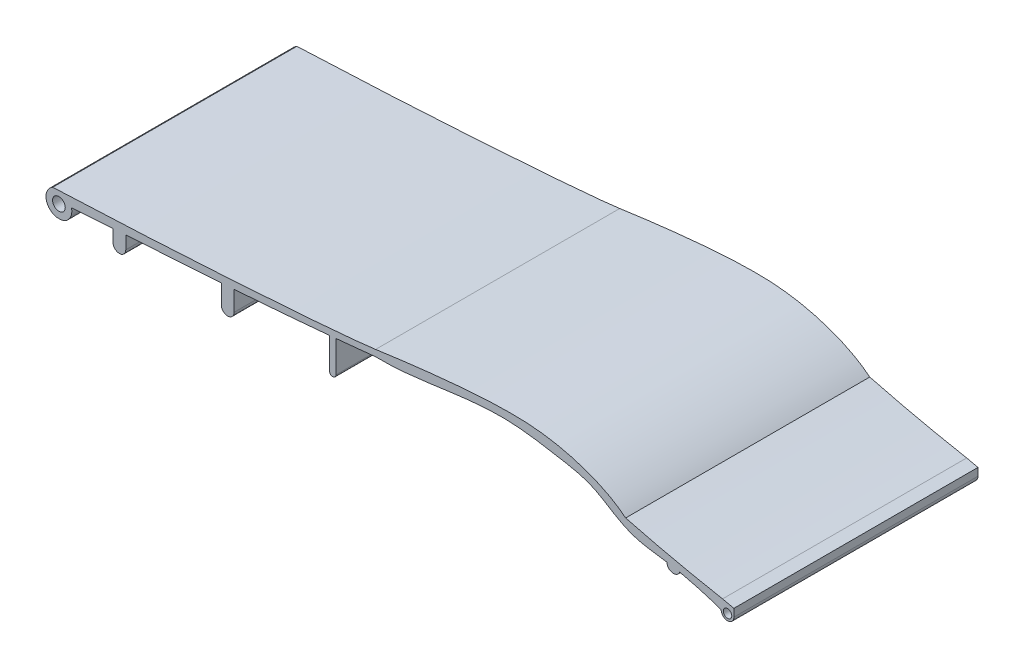
SolidWorks part; units mm, degrees
material "Balsa"
ref_plane "Front Plane" through (0, 0, 0) normal (0, 0, 1) x (1, 0, 0)
ref_plane "Top Plane" through (0, 0, 0) normal (0, 1, 0) x (1, 0, 0)
ref_plane "Right Plane" through (0, 0, 0) normal (1, 0, 0) x (0, 0, -1)
sketch "Sketch1" plane through (0, 0, 0) normal (0, 0, 1) x (1, 0, 0)
  line L0 (-268, 0) -> (-274, 0)
  line L1 (-274, 0) -> (-280, 0)
  line L2 (-280, 0) -> (-280, 11.2166)
  line L3 (-274, 5.4595) -> (-274, 6)
  line L5 (-274, 6) -> (-274, 5.4595)
  line L6 (-274, 6) -> (-274, 5.4595)
  line L8 (-70, 16) -> (-70, -46.5)
  line L9 (-70, -46.5) -> (-58, -46.5)
  line L10 (-58, -46.5) -> (-58, 16)
  line L11 (-58, 16) -> (-70, 16)
  line L70 (150, -10) -> (150, -20)
  line L71 (150, 0) -> (150, -10)
  line L72 (-7, 3.5) -> (-7, -46.5)
  line L73 (-7, 11.3618) -> (-7, 3.5)
  line L74 (0, 0) -> (-200, 0)
  line L75 (0, 0) -> (-200, 0)
  line L76 (0, 0) -> (150, 0)
  line L77 (0, 0) -> (-570, 0)
  line L78 (-7, -46.5) -> (38, -46.5)
  line L79 (38, -46.5) -> (38, 0)
  line L80 (38, 0) -> (44, 0)
  line L81 (44, 0) -> (44, -46.5)
  line L82 (44, -46.5) -> (38, -46.5)
  line L83 (-7, -46.5) -> (-13, -46.5)
  line L84 (-13, -46.5) -> (-13, 3.5)
  line L85 (-121, -46.5) -> (-166, -46.5)
  line L86 (-121, -46.5) -> (-121, 17)
  line L87 (-121, 17) -> (-115, 17)
  line L88 (-115, 17) -> (-115, -46.5)
  line L89 (-115, -46.5) -> (-121, -46.5)
  line L90 (-172, -46.5) -> (-166, -46.5)
  line L91 (-166, -46.5) -> (-166, 0)
  line L92 (-166, 0) -> (-172, 0)
  line L93 (-223, -46.5) -> (-217, -46.5)
  line L94 (-223, -46.5) -> (-268, -46.5)
  line L95 (-223, 0) -> (-223, -46.5)
  line L96 (-172, -46.5) -> (-217, -46.5)
  line L97 (-172, 0) -> (-172, -46.5)
  line L98 (-217, 0) -> (-223, 0)
  line L99 (-268, 0) -> (-223, 0)
  line L100 (-217, 0) -> (-172, 0)
  line L101 (-217, -46.5) -> (-217, 0)
  line L102 (150, 0) -> (-570, 0)
  line L103 (-274, 5.4595) -> (-274, 6)
  line L105 (-570.0024, 16.2157) -> (-570.0015, 10.2157)
  line L106 (-570.0024, 16.2157) -> (-570, 0)
  line L107 (150, -20) -> (150, -55)
  line L108 (150, -55) -> (150, -65)
  line L109 (150, -20) -> (150, 0)
  line L110 (-200, 0) -> (-200, -87.1417)
  line L111 (-200, -87.1417) -> (-200, 15.2435)
  line L112 (-124.7856, 21.2375) -> (-121, 17)
  line L113 (44, -89.7516) -> (44, -99.7516)
  line L114 (44, -99.7516) -> (-91, -99.7516)
  line L115 (-91, -99.7516) -> (-91, -89.7516)
  line L116 (-91, -89.7516) -> (44, -89.7516)
  line L117 (44, -59.7516) -> (-91, -59.7516)
  line L118 (-91, -59.7516) -> (-91, -89.7516)
  line L119 (44, -59.7516) -> (44, -89.7516)
  line L120 (44, -89.7516) -> (44, -59.7516)
  line L121 (44, -10.7516) -> (44, -59.7516)
  line L122 (44, -10.7516) -> (44, -59.7516)
  line L123 (44, -10.7516) -> (44, -59.7516)
  line L124 (44, -46.5) -> (-274, -46.5)
  line L125 (-274, 0) -> (-274, -46.5)
  line L126 (-274, -46.5) -> (-268, -46.5)
  line L127 (-286.4605, 10.9659) -> (-286.4605, 4.5334)
  line L128 (-268, 0) -> (-268, 8.629)
  line L129 (-268, -46.5) -> (-268, 0)
  line L130 (-268, 0) -> (-274, 0)
  line L131 (-426, -11.2496) -> (-426, -41.2496)
  line L132 (44, -10.7516) -> (38, -10.7516)
  line L135 (-7, 11.3618) -> (44, 0)
  line L136 (44, 0) -> (44, -10.7516)
  line L137 (38, -10.7516) -> (38, -3.6013)
  circle A0 centre (-274, 6) radius 3
  circle A2 centre (-10, 3.5) radius 3
  arc A4 (-7, 11.3618) -> (150, -10) centre (160.7975, 656.9795) ccw
  arc A5 (-570.0015, 10.2157) -> (-280, 5.0011) centre (-396.8357, 1573.962) ccw
  arc A6 (-268, 8.629) -> (-124.7856, 18.2375) centre (-325.5367, 1938.3319) ccw
  circle A7 centre (41, -3.6013) radius 3
  spline S2 degree 3 poles (150, -65) (75.3181, -107.9793) (-174.9356, -104.3379) (-414.0206, -49.0474) (-570, 0) knots 0 0 0 0 0.3348 1 1 1 1
  spline S3 degree 3 poles (-124.7856, 21.2375) (-153.5511, 17.0681) (-428.6382, -2.4062) (-576.2077, 17) knots 0 0 0 0 1 1 1 1
  spline S5 degree 3 poles (-199.3437, 0.495) (-200.1813, -0.1291) (-199.226, 0.5194) (-198.369, 1.0376) (-196.1381, 2.3769) (-193.1122, 3.8252) (-188.8712, 5.408) (-183.689, 6.8909) (-177.6267, 8.2768) (-170.7959, 9.4967) (-163.2767, 10.5098) (-155.1671, 11.2868) (-146.5636, 11.7978) (-137.5696, 12.0361) (-128.2881, 11.9963) (-118.8227, 11.681) (-109.2761, 11.1075) (-99.7479, 10.2984) (-90.3339, 9.2749) (-81.1229, 8.0828) (-72.1978, 6.7569) (-63.6354, 5.3459) (-55.5023, 3.8968) (-47.8581, 2.464) (-40.7509, 1.107) (-34.2154, -0.1398) (-28.2189, -1.1341) (-22.7323, -1.8456) (-17.7581, -2.4003) (-13.3207, -2.8103) (-9.4655, -3.0663) (-6.2354, -3.2056) (-3.6668, -3.1153) (-1.7892, -3.0221) (-0.3927, -2.3577) (-0.017, -1.0193) (0.0467, 0.4399) (-0.2836, 2.1653) (-0.9767, 4.0346) (-2.0583, 6.0034) (-3.5225, 8.0271) (-5.4287, 10.0433) (-7.7678, 12.0345) (-10.506, 14.0225) (-13.642, 15.9651) (-17.1562, 17.836) (-21.0295, 19.6139) (-25.2494, 21.2627) (-29.7898, 22.7737) (-34.6314, 24.1113) (-39.7536, 25.2521) (-45.1512, 26.1326) (-50.8254, 26.7554) (-56.7995, 27.0627) (-63.0757, 27.0793) (-69.6422, 26.9233) (-76.4655, 26.562) (-83.5076, 26.0368) (-90.7283, 25.3757) (-98.0768, 24.616) (-105.4932, 23.7718) (-112.9161, 22.8645) (-120.2861, 21.8877) (-127.55, 20.8444) (-134.6611, 19.7429) (-141.5735, 18.5812) (-148.2473, 17.3741) (-154.6405, 16.1233) (-160.7158, 14.8443) (-166.4359, 13.5437) (-171.7669, 12.2295) (-176.6782, 10.9112) (-181.1426, 9.6011) (-185.1352, 8.3052) (-188.6352, 7.0347) (-191.6263, 5.7987) (-194.104, 4.6144) (-196.0965, 3.3923) (-197.5531, 2.1801) (-198.7877, 1.0405) (-199.3437, 0.495) (-200.1813, -0.1291) (-199.226, 0.5194) knots -0.007483 -0.003649 -0.00098 0 0.001 0.004147 0.009748 0.018044 0.028864 0.041831 0.056714 0.073341 0.091508 0.111022 0.131662 0.153208 0.175433 0.19811 0.221011 0.243906 0.266573 0.28881 0.310405 0.331178 0.350944 0.369556 0.386865 0.402753 0.417196 0.43038 0.442363 0.453032 0.462284 0.470026 0.476177 0.48065 0.483553 0.486421 0.489953 0.494097 0.498851 0.504197 0.510125 0.516691 0.524012 0.532092 0.540898 0.550403 0.560581 0.571396 0.582828 0.59483 0.607347 0.620384 0.633969 0.6482 0.663194 0.678899 0.695227 0.712113 0.729459 0.747143 0.76501 0.782905 0.800688 0.818242 0.835449 0.852212 0.86843 0.884009 0.898855 0.912882 0.926011 0.938167 0.94929 0.959322 0.968217 0.975948 0.982474 0.987905 0.992517 0.996351 0.99902 1 1.001 1.004147 1.009748 only from (-200, 0) to (-200, 0)
  spline S6 degree 3 poles (-124.7856, 18.2375) (-104.0824, 17.7332) (-77.2395, 25.8381) (-49.0695, 22.1621) (-28.3585, 18.6444) (-22.2812, 16.9142) (-2.3267, 3.4627) (13.669, 4.5429) (37.1337, -3.1314) (38, -3.6013) knots 0 0 0 0 0.28574 0.361508 0.389511 0.565774 0.659519 0.859319 1 1 1 1
  dimension "D3" = 3
extrude "Boss-Extrude1" add sketch "Sketch1" along normal mid plane 115
sketch "Sketch2" plane through (0, 0, 57.5) normal (0, 0, 1) x (1, 0, 0)
  circle A0 centre (41, -3.6013) radius 2
extrude "Cut-Extrude1" cut sketch "Sketch2" against normal blind 115
sketch "Sketch3" plane through (0, 0, 57.5) normal (0, 0, 1) x (1, 0, 0)
  line L0 (-274, 12.0826) -> (-297.0333, 12.0826)
  line L1 (-297.0333, 12.0826) -> (-297.0333, -10.4449)
  line L2 (-297.0333, -10.4449) -> (-274, -10.4449)
  line L3 (-274, -10.4449) -> (-274, -0.0826)
  line L4 (-200, 11.8574) -> (-268.0857, 7.4206)
  line L5 (-274, -10.4449) -> (-200, -10.4449)
  line L6 (-200, -10.4449) -> (-200, 11.8574)
  circle A0 centre (-274, 6) radius 6.0826
  spline M7 degree 3 poles (-124.7856, 21.2375) (-153.5511, 17.0681) (-428.6382, -2.4062) (-576.2077, 17) knots 0 0 0 0 1 1 1 1 only from (-124.7856, 21.2375) to (-286.4605, 10.9659)
  line M8 (-286.4605, 10.9659) -> (-286.4605, 4.5334)
  arc M9 (-286.4605, 4.5334) -> (-280, 5.0011) centre (-396.8357, 1573.962) ccw
  line M10 (-280, 5.0011) -> (-280, 0)
  line M11 (-280, 0) -> (-200, 0)
  line M12 (-200, 0) -> (-200, 11.8574)
extrude "Cut-Extrude2" cut sketch "Sketch3" against normal up to surface (115 mm away) contours A0 M7 M8 M9 | A0 M10 M11 | A0 L4 M11 M12
sketch "Sketch4" plane through (0, 0, 0) normal (0, 0, 1) x (1, 0, 0)
  line L0 (0, 0) -> (-200, 0) construction
  line L1 (0, 0) -> (-200, 0) construction
  line L2 (-200, 0) -> (-200, -87.1417) construction
  line L3 (-200, -87.1417) -> (-200, 15.2435) construction
  line L4 (-70, 16) -> (-70, -46.5)
  line L5 (-70, -46.5) -> (-58, -46.5)
  line L6 (-58, -46.5) -> (-58, 16)
  line L7 (-58, 16) -> (-70, 16)
  line L8 (-70, 16) -> (-70, -46.5)
  line L9 (-70, -46.5) -> (-58, -46.5)
  line L10 (-58, -46.5) -> (-58, 16)
  line L11 (-58, 16) -> (-70, 16)
  line L12 (0, 0) -> (150, 0) construction
  line L13 (0, 0) -> (-570, 0) construction
  line L14 (-7, 3.5) -> (-7, -46.5) construction
  line L15 (-7, 11.3618) -> (-7, 3.5) construction
  line L16 (-7, 11.3618) -> (44, 0) construction
  line L17 (-7, -46.5) -> (38, -46.5) construction
  line L18 (-7, -46.5) -> (-13, -46.5) construction
  line L19 (-13, -46.5) -> (-13, 3.5) construction
  line L20 (150, 0) -> (150, -10) construction
  line L21 (150, 0) -> (-570, 0) construction
  line L22 (150, -20) -> (150, 0) construction
  line L23 (150, -10) -> (150, -20) construction
  line L24 (150, -20) -> (150, -55) construction
  line L25 (150, -55) -> (150, -65) construction
  line L26 (-223, -46.5) -> (-217, -46.5) construction
  line L27 (-223, -46.5) -> (-268, -46.5) construction
  line L28 (-223, 0) -> (-223, -46.5) construction
  line L29 (-166, -46.5) -> (-166, 0) construction
  line L30 (-166, 0) -> (-172, 0) construction
  line L31 (-172, 0) -> (-172, -46.5) construction
  line L32 (-217, 0) -> (-172, 0) construction
  line L33 (-172, -46.5) -> (-166, -46.5) construction
  line L34 (-172, -46.5) -> (-217, -46.5) construction
  line L35 (-121, -46.5) -> (-121, 17) construction
  line L36 (-121, 17) -> (-115, 17) construction
  line L37 (-115, 17) -> (-115, -46.5) construction
  line L38 (-115, -46.5) -> (-121, -46.5) construction
  line L39 (-124.7856, 21.2375) -> (-121, 17) construction
  line L40 (-121, -46.5) -> (-166, -46.5) construction
  line L41 (44, 0) -> (44, -46.5) construction
  line L42 (44, -46.5) -> (38, -46.5) construction
  line L43 (44, -46.5) -> (-274, -46.5) construction
  line L44 (38, -46.5) -> (38, 0) construction
  line L45 (38, 0) -> (44, 0) construction
  line L46 (44, 0) -> (44, -10.7516) construction
  line L47 (-570.0024, 16.2157) -> (-570.0015, 10.2157) construction
  line L48 (-570.0024, 16.2157) -> (-570, 0) construction
  line L49 (-217, 0) -> (-223, 0) construction
  line L50 (-217, -46.5) -> (-217, 0) construction
  line L51 (-268, 0) -> (-223, 0) construction
  line L52 (-274, -46.5) -> (-268, -46.5) construction
  line L53 (-268, -46.5) -> (-268, 0) construction
  line L54 (-274, 5.4595) -> (-274, 6) construction
  line L55 (-274, 6) -> (-274, 5.4595) construction
  line L56 (-274, 6) -> (-274, 5.4595) construction
  line L57 (-274, 5.4595) -> (-274, 6) construction
  line L58 (-268, 0) -> (-274, 0) construction
  line L59 (-274, 0) -> (-280, 0) construction
  line L60 (-280, 0) -> (-280, 11.2166) construction
  line L61 (-274, 0) -> (-274, -46.5) construction
  line L62 (-268, 0) -> (-274, 0) construction
  line L63 (44, -10.7516) -> (38, -10.7516) construction
  line L64 (38, -10.7516) -> (38, -3.6013) construction
  line L65 (-268, 0) -> (-268, 8.629) construction
  line L66 (-426, -11.2496) -> (-426, -41.2496) construction
  line L67 (-286.4605, 10.9659) -> (-286.4605, 4.5334) construction
  line L68 (44, -10.7516) -> (44, -59.7516) construction
  line L69 (44, -10.7516) -> (44, -59.7516) construction
  line L70 (44, -10.7516) -> (44, -59.7516) construction
  line L71 (44, -59.7516) -> (-91, -59.7516) construction
  line L72 (-91, -59.7516) -> (-91, -89.7516) construction
  line L73 (44, -59.7516) -> (44, -89.7516) construction
  line L74 (44, -89.7516) -> (44, -59.7516) construction
  line L75 (44, -89.7516) -> (44, -99.7516) construction
  line L76 (44, -99.7516) -> (-91, -99.7516) construction
  line L77 (-91, -99.7516) -> (-91, -89.7516) construction
  line L78 (-91, -89.7516) -> (44, -89.7516) construction
  line L79 (0, 0) -> (-200, 0)
  line L80 (0, 0) -> (-200, 0)
  line L81 (-200, 0) -> (-200, -87.1417)
  line L82 (-200, -87.1417) -> (-200, 15.2435)
  line L83 (0, 0) -> (150, 0)
  line L84 (0, 0) -> (-570, 0)
  line L85 (-7, 3.5) -> (-7, -46.5)
  line L86 (-7, 11.3618) -> (-7, 3.5)
  line L87 (-7, 11.3618) -> (44, 0)
  line L88 (-7, -46.5) -> (38, -46.5)
  line L89 (-7, -46.5) -> (-13, -46.5)
  line L90 (-13, -46.5) -> (-13, 3.5)
  line L91 (150, 0) -> (150, -10)
  line L92 (150, 0) -> (-570, 0)
  line L93 (150, -20) -> (150, 0)
  line L94 (150, -10) -> (150, -20)
  line L95 (150, -20) -> (150, -55)
  line L96 (150, -55) -> (150, -65)
  line L97 (-223, -46.5) -> (-217, -46.5)
  line L98 (-223, -46.5) -> (-268, -46.5)
  line L99 (-223, 0) -> (-223, -46.5)
  line L100 (-166, -46.5) -> (-166, 0)
  line L101 (-166, 0) -> (-172, 0)
  line L102 (-172, 0) -> (-172, -46.5)
  line L103 (-217, 0) -> (-172, 0)
  line L104 (-172, -46.5) -> (-166, -46.5)
  line L105 (-172, -46.5) -> (-217, -46.5)
  line L106 (-121, -46.5) -> (-121, 17)
  line L107 (-121, 17) -> (-115, 17)
  line L108 (-115, 17) -> (-115, -46.5)
  line L109 (-115, -46.5) -> (-121, -46.5)
  line L110 (-124.7856, 21.2375) -> (-121, 17)
  line L111 (-121, -46.5) -> (-166, -46.5)
  line L112 (44, 0) -> (44, -46.5)
  line L113 (44, -46.5) -> (38, -46.5)
  line L114 (44, -46.5) -> (-274, -46.5)
  line L115 (38, -46.5) -> (38, 0)
  line L116 (38, 0) -> (44, 0)
  line L117 (44, 0) -> (44, -10.7516)
  line L118 (-570.0024, 16.2157) -> (-570.0015, 10.2157)
  line L119 (-570.0024, 16.2157) -> (-570, 0)
  line L120 (-217, 0) -> (-223, 0)
  line L121 (-217, -46.5) -> (-217, 0)
  line L122 (-268, 0) -> (-223, 0)
  line L123 (-274, -46.5) -> (-268, -46.5)
  line L124 (-268, -46.5) -> (-268, 0)
  line L125 (-274, 5.4595) -> (-274, 6)
  line L126 (-274, 6) -> (-274, 5.4595)
  line L127 (-274, 6) -> (-274, 5.4595)
  line L128 (-274, 5.4595) -> (-274, 6)
  line L129 (-268, 0) -> (-274, 0)
  line L130 (-274, 0) -> (-280, 0)
  line L131 (-280, 0) -> (-280, 11.2166)
  line L132 (-274, 0) -> (-274, -46.5)
  line L133 (-268, 0) -> (-274, 0)
  line L134 (44, -10.7516) -> (38, -10.7516)
  line L135 (38, -10.7516) -> (38, -3.6013)
  line L136 (-268, 0) -> (-268, 8.629)
  line L137 (-426, -11.2496) -> (-426, -41.2496)
  line L138 (-286.4605, 10.9659) -> (-286.4605, 4.5334)
  line L139 (44, -10.7516) -> (44, -59.7516)
  line L140 (44, -10.7516) -> (44, -59.7516)
  line L141 (44, -10.7516) -> (44, -59.7516)
  line L142 (44, -59.7516) -> (-91, -59.7516)
  line L143 (-91, -59.7516) -> (-91, -89.7516)
  line L144 (44, -59.7516) -> (44, -89.7516)
  line L145 (44, -89.7516) -> (44, -59.7516)
  line L146 (44, -89.7516) -> (44, -99.7516)
  line L147 (44, -99.7516) -> (-91, -99.7516)
  line L148 (-91, -99.7516) -> (-91, -89.7516)
  line L149 (-91, -89.7516) -> (44, -89.7516)
  line L150 (-268, 0) -> (-223, 0)
  line L151 (-245.5, 0) -> (-242.5, 0)
  line L152 (-242.5, 0) -> (-242.5, 9.5581)
  line L153 (-242.5, 9.5581) -> (-242.5, 0)
  line L154 (-245.5, 0) -> (-248.5, 0)
  line L155 (-248.5, 0) -> (-248.5, 9.3091)
  line L156 (-217, 0) -> (-172, 0)
  line L157 (-194.5, 0) -> (-197.5, 0)
  line L158 (-197.5, 0) -> (-197.5, 12.0219)
  line L159 (-197.5, 12.0219) -> (-197.5, 0)
  line L160 (-194.5, 0) -> (-191.5, 0)
  line L161 (-191.5, 0) -> (-191.5, 12.4301)
  line L162 (-191.5, 12.4301) -> (-191.5, 0)
  line L163 (-166, 0) -> (-121, 0)
  line L164 (-121, 0) -> (-143.5, 0)
  line L165 (-143.5, 0) -> (-146.5, 0)
  line L166 (-146.5, 0) -> (-146.5, 16.0912)
  line L167 (-146.5, 16.0912) -> (-146.5, 0)
  line L168 (-143.5, 0) -> (-143.5, 16.3729)
  line L169 (38, -46.5) -> (44, -46.5)
  line L170 (-7, 0) -> (38, 0)
  line L171 (15.5, 0) -> (18.4636, 0)
  line L172 (18.4636, 0) -> (12.4636, 0)
  line L173 (12.4636, 0) -> (12.4636, 3.0608)
  line L174 (12.4636, 3.0608) -> (12.4636, 0)
  line L175 (18.4636, 0) -> (18.4636, 1.999)
  arc A0 (-7, 11.3618) -> (150, -10) centre (160.7975, 656.9795) ccw construction
  circle A1 centre (-10, 3.5) radius 3
  circle A2 centre (-10, 3.5) radius 3
  circle A3 centre (41, -3.6013) radius 3
  circle A4 centre (41, -3.6013) radius 3
  circle A5 centre (-274, 6) radius 3
  circle A6 centre (-274, 6) radius 3
  arc A7 (-570.0015, 10.2157) -> (-280, 5.0011) centre (-396.8357, 1573.962) ccw construction
  arc A8 (-268, 8.629) -> (-124.7856, 18.2375) centre (-325.5367, 1938.3319) ccw construction
  arc A9 (-7, 11.3618) -> (150, -10) centre (160.7975, 656.9795) ccw
  arc A10 (-570.0015, 10.2157) -> (-280, 5.0011) centre (-396.8357, 1573.962) ccw
  arc A11 (-268, 8.629) -> (-124.7856, 18.2375) centre (-325.5367, 1938.3319) ccw
  spline S0 degree 3 poles (256.4857, 2895.1761) (618.7233, -57.6038) (-940.8706, -361.8959) (-2105.0138, 1162.5643) (-3368.7302, 2.2126) knots -1.060607 -1.060607 -1.060607 -1.060607 0.3348 4.889787 4.889787 4.889787 4.889787 only from (150, -65) to (-570, 0) construction
  spline S1 degree 3 poles (-199.3437, 0.495) (-200.1813, -0.1291) (-199.226, 0.5194) (-198.369, 1.0376) (-196.1381, 2.3769) (-193.1122, 3.8252) (-188.8712, 5.408) (-183.689, 6.8909) (-177.6267, 8.2768) (-170.7959, 9.4967) (-163.2767, 10.5098) (-155.1671, 11.2868) (-146.5636, 11.7978) (-137.5696, 12.0361) (-128.2881, 11.9963) (-118.8227, 11.681) (-109.2761, 11.1075) (-99.7479, 10.2984) (-90.3339, 9.2749) (-81.1229, 8.0828) (-72.1978, 6.7569) (-63.6354, 5.3459) (-55.5023, 3.8968) (-47.8581, 2.464) (-40.7509, 1.107) (-34.2154, -0.1398) (-28.2189, -1.1341) (-22.7323, -1.8456) (-17.7581, -2.4003) (-13.3207, -2.8103) (-9.4655, -3.0663) (-6.2354, -3.2056) (-3.6668, -3.1153) (-1.7892, -3.0221) (-0.3927, -2.3577) (-0.017, -1.0193) (0.0467, 0.4399) (-0.2836, 2.1653) (-0.9767, 4.0346) (-2.0583, 6.0034) (-3.5225, 8.0271) (-5.4287, 10.0433) (-7.7678, 12.0345) (-10.506, 14.0225) (-13.642, 15.9651) (-17.1562, 17.836) (-21.0295, 19.6139) (-25.2494, 21.2627) (-29.7898, 22.7737) (-34.6314, 24.1113) (-39.7536, 25.2521) (-45.1512, 26.1326) (-50.8254, 26.7554) (-56.7995, 27.0627) (-63.0757, 27.0793) (-69.6422, 26.9233) (-76.4655, 26.562) (-83.5076, 26.0368) (-90.7283, 25.3757) (-98.0768, 24.616) (-105.4932, 23.7718) (-112.9161, 22.8645) (-120.2861, 21.8877) (-127.55, 20.8444) (-134.6611, 19.7429) (-141.5735, 18.5812) (-148.2473, 17.3741) (-154.6405, 16.1233) (-160.7158, 14.8443) (-166.4359, 13.5437) (-171.7669, 12.2295) (-176.6782, 10.9112) (-181.1426, 9.6011) (-185.1352, 8.3052) (-188.6352, 7.0347) (-191.6263, 5.7987) (-194.104, 4.6144) (-196.0965, 3.3923) (-197.5531, 2.1801) (-198.7877, 1.0405) (-199.3437, 0.495) (-200.1813, -0.1291) (-199.226, 0.5194) knots -0.007483 -0.003649 -0.00098 0 0.001 0.004147 0.009748 0.018044 0.028864 0.041831 0.056714 0.073341 0.091508 0.111022 0.131662 0.153208 0.175433 0.19811 0.221011 0.243906 0.266573 0.28881 0.310405 0.331178 0.350944 0.369556 0.386865 0.402753 0.417196 0.43038 0.442363 0.453032 0.462284 0.470026 0.476177 0.48065 0.483553 0.486421 0.489953 0.494097 0.498851 0.504197 0.510125 0.516691 0.524012 0.532092 0.540898 0.550403 0.560581 0.571396 0.582828 0.59483 0.607347 0.620384 0.633969 0.6482 0.663194 0.678899 0.695227 0.712113 0.729459 0.747143 0.76501 0.782905 0.800688 0.818242 0.835449 0.852212 0.86843 0.884009 0.898855 0.912882 0.926011 0.938167 0.94929 0.959322 0.968217 0.975948 0.982474 0.987905 0.992517 0.996351 0.99902 1 1.001 1.004147 1.009748 only from (-200, 0) to (-200, 0)
  spline S2 degree 3 poles (-199.3437, 0.495) (-200.1813, -0.1291) (-199.226, 0.5194) (-198.369, 1.0376) (-196.1381, 2.3769) (-193.1122, 3.8252) (-188.8712, 5.408) (-183.689, 6.8909) (-177.6267, 8.2768) (-170.7959, 9.4967) (-163.2767, 10.5098) (-155.1671, 11.2868) (-146.5636, 11.7978) (-137.5696, 12.0361) (-128.2881, 11.9963) (-118.8227, 11.681) (-109.2761, 11.1075) (-99.7479, 10.2984) (-90.3339, 9.2749) (-81.1229, 8.0828) (-72.1978, 6.7569) (-63.6354, 5.3459) (-55.5023, 3.8968) (-47.8581, 2.464) (-40.7509, 1.107) (-34.2154, -0.1398) (-28.2189, -1.1341) (-22.7323, -1.8456) (-17.7581, -2.4003) (-13.3207, -2.8103) (-9.4655, -3.0663) (-6.2354, -3.2056) (-3.6668, -3.1153) (-1.7892, -3.0221) (-0.3927, -2.3577) (-0.017, -1.0193) (0.0467, 0.4399) (-0.2836, 2.1653) (-0.9767, 4.0346) (-2.0583, 6.0034) (-3.5225, 8.0271) (-5.4287, 10.0433) (-7.7678, 12.0345) (-10.506, 14.0225) (-13.642, 15.9651) (-17.1562, 17.836) (-21.0295, 19.6139) (-25.2494, 21.2627) (-29.7898, 22.7737) (-34.6314, 24.1113) (-39.7536, 25.2521) (-45.1512, 26.1326) (-50.8254, 26.7554) (-56.7995, 27.0627) (-63.0757, 27.0793) (-69.6422, 26.9233) (-76.4655, 26.562) (-83.5076, 26.0368) (-90.7283, 25.3757) (-98.0768, 24.616) (-105.4932, 23.7718) (-112.9161, 22.8645) (-120.2861, 21.8877) (-127.55, 20.8444) (-134.6611, 19.7429) (-141.5735, 18.5812) (-148.2473, 17.3741) (-154.6405, 16.1233) (-160.7158, 14.8443) (-166.4359, 13.5437) (-171.7669, 12.2295) (-176.6782, 10.9112) (-181.1426, 9.6011) (-185.1352, 8.3052) (-188.6352, 7.0347) (-191.6263, 5.7987) (-194.104, 4.6144) (-196.0965, 3.3923) (-197.5531, 2.1801) (-198.7877, 1.0405) (-199.3437, 0.495) (-200.1813, -0.1291) (-199.226, 0.5194) knots -0.007483 -0.003649 -0.00098 0 0.001 0.004147 0.009748 0.018044 0.028864 0.041831 0.056714 0.073341 0.091508 0.111022 0.131662 0.153208 0.175433 0.19811 0.221011 0.243906 0.266573 0.28881 0.310405 0.331178 0.350944 0.369556 0.386865 0.402753 0.417196 0.43038 0.442363 0.453032 0.462284 0.470026 0.476177 0.48065 0.483553 0.486421 0.489953 0.494097 0.498851 0.504197 0.510125 0.516691 0.524012 0.532092 0.540898 0.550403 0.560581 0.571396 0.582828 0.59483 0.607347 0.620384 0.633969 0.6482 0.663194 0.678899 0.695227 0.712113 0.729459 0.747143 0.76501 0.782905 0.800688 0.818242 0.835449 0.852212 0.86843 0.884009 0.898855 0.912882 0.926011 0.938167 0.94929 0.959322 0.968217 0.975948 0.982474 0.987905 0.992517 0.996351 0.99902 1 1.001 1.004147 1.009748 only from (-200, 0) to (-200, 0)
  spline S3 degree 3 poles (-3110.7255, -266.392) (3990.0191, 486.8646) (-4765.8675, -664.7648) (2288.7409, 868.6589) knots -1.540196 -1.540196 -1.540196 -1.540196 2.851592 2.851592 2.851592 2.851592 only from (-124.7856, 21.2375) to (-576.2077, 17) construction
  spline S4 degree 3 poles (-261.6134, 3004.9013) (-350.8, -270.6526) (-190.9586, 40.6775) (-49.0695, 22.1621) (-28.3585, 18.6444) (-22.2812, 16.9142) (-2.3267, 3.4627) (43.1844, 6.5361) (208.0549, -86.4397) (-2781.9641, 1018.9817) knots -1.57241 -1.57241 -1.57241 -1.57241 0.28574 0.361508 0.389511 0.565774 0.659519 0.859319 1.801236 1.801236 1.801236 1.801236 only from (-124.7856, 18.2375) to (38, -3.6013) construction
  spline S5 degree 3 poles (150, -65) (75.3181, -107.9793) (-174.9356, -104.3379) (-414.0206, -49.0474) (-570, 0) knots 0 0 0 0 0.3348 1 1 1 1
  spline S6 degree 3 poles (-124.7856, 21.2375) (-153.5511, 17.0681) (-428.6382, -2.4062) (-576.2077, 17) knots 0 0 0 0 1 1 1 1
  spline S7 degree 3 poles (-124.7856, 18.2375) (-104.0824, 17.7332) (-77.2395, 25.8381) (-49.0695, 22.1621) (-28.3585, 18.6444) (-22.2812, 16.9142) (-2.3267, 3.4627) (13.669, 4.5429) (37.1337, -3.1314) (38, -3.6013) knots 0 0 0 0 0.28574 0.361508 0.389511 0.565774 0.659519 0.859319 1 1 1 1
  dimension "D1" = 0
  dimension "D2" = 0
  dimension "D3" = 0
  dimension "D4" = 0
  dimension "D5" = 0
extrude "Boss-Extrude2" add sketch "Sketch4" along normal mid plane 115 contours A11 L155 L92 L150 L152 | S2 L161 A11 L158 | L159 S2 L162 | S2 L158 L156 L161 | S2 L166 L163 L168 | L167 S2 L168 A11 | A11 S7 L110 S2 | S7 L173 L170 L175
fillet "Fillet1" radius 3 4 edges at (-191.5, 0, 0) (-197.5, 0, 0) (-242.5, 0, 0) (-248.5, 0, 0)
fillet "Fillet2" radius 3 2 edges at (12.4636, 0, 0) (18.4636, 0, 0)
fillet "Fillet3" radius 1.5 2 edges at (-143.5, 0, 0) (-146.5, 0, 0)
